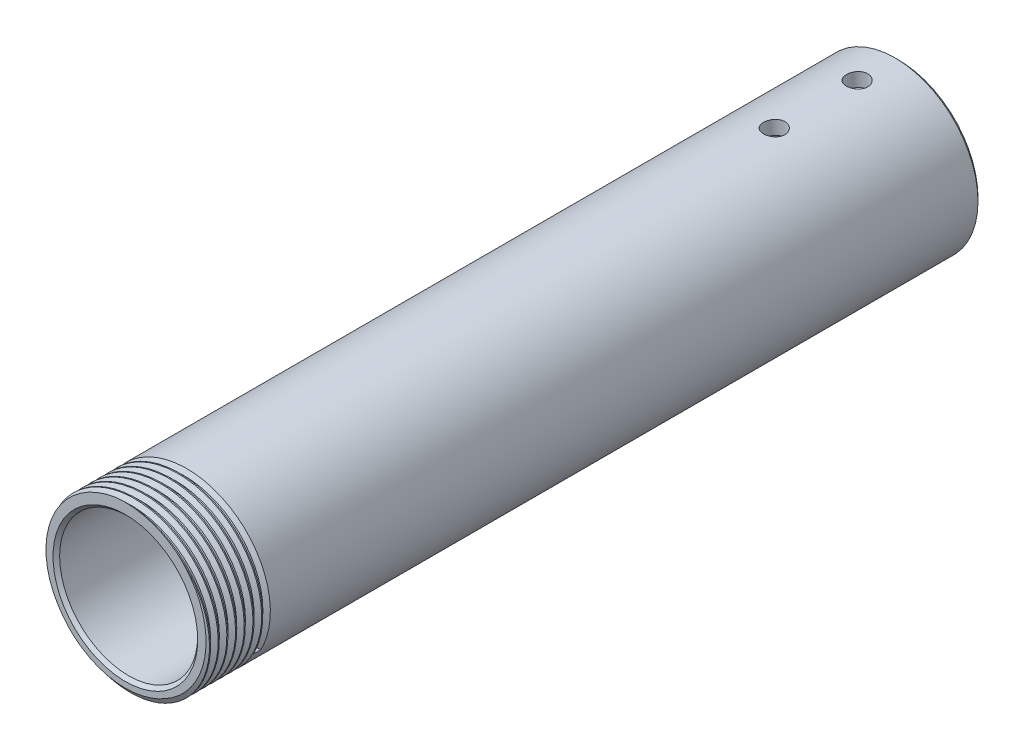
SolidWorks part; units mm, degrees
material "6061-T6 (SS)"
ref_plane "Front Plane" through (0, 0, 0) normal (0, 0, 1) x (1, 0, 0)
ref_plane "Top Plane" through (0, 0, 0) normal (0, 1, 0) x (1, 0, 0)
ref_plane "Right Plane" through (0, 0, 0) normal (1, 0, 0) x (0, 0, -1)
sketch "Sketch1" plane through (0, 0, 0) normal (0, 0, 1) x (1, 0, 0)
  circle A0 centre (0, 0) radius 15.875
  circle A1 centre (0, 0) radius 19.05
  dimension "D1" = 31.75
  dimension "D2" = 3.175
extrude "Boss-Extrude1" add sketch "Sketch1" along normal blind 177.8
ref_plane "Rear Tangent Plane" through (0, 19.05, 0) normal (0, 1, 0) x (1, 0, 0)
hole_wizard "#8 Clearance Hole1" positions "Sketch2" profile "Sketch3" hole size "#8" standard "ANSI Inch" end condition through all
sketch "Sketch2" plane through (0, 19.05, 0) normal (0, 1, 0) x (1, 0, 0)
  point P0 (0, -9.525)
  point P3 (0, -28.575)
sketch "Sketch3" plane through (0, 19.05, 9.525) normal (1, 0, 0) x (0, 0, 1)
  line L0 (0, 0) -> (0, 38.1)
  line L1 (0, 38.1) -> (2.4574, 38.1)
  line L2 (2.4574, 38.1) -> (2.4574, 0)
  line L5 (2.4574, 0) -> (0, 0)
  line L11 (0, -6.35) -> (0, 107.95) construction
  dimension "Thru Hole Dia." = 4.9149
  dimension "Thru Hole Depth" = 38.1
ref_plane "FWD Tangent Plane" through (0, -19.05, 0) normal (0, -1, 0) x (-1, 0, 0)
hole_wizard "#8 Clearance Hole2" positions "Sketch4" profile "Sketch5" hole size "#8" standard "ANSI Inch"
sketch "Sketch4" plane through (0, -19.05, 0) normal (0, -1, 0) x (-1, 0, 0)
  circle A0 centre (0, -107.1562) radius 2.4574 construction
  circle A1 centre (0, -69.0562) radius 2.4575 construction
  point P0 (0, -107.1562)
  point P2 (0, -69.0562)
sketch "Sketch5" plane through (0, -19.05, 107.1562) normal (1, 0, 0) x (0, 0, -1)
  line L0 (0, 0) -> (0, 3.175)
  line L1 (0, 3.175) -> (2.4574, 3.175)
  line L2 (2.4574, 3.175) -> (2.4574, 0)
  line L5 (2.4574, 0) -> (0, 0)
  line L11 (0, -6.35) -> (0, 107.95) construction
  dimension "Thru Hole Dia." = 4.9149
  dimension "Thru Hole Depth" = 3.175
hole_wizard "1/2 (0.5) Diameter Hole1" positions "Sketch6" profile "Sketch7" hole size "1/2" standard "ANSI Inch"
sketch "Sketch6" plane through (0, -19.05, 0) normal (0, -1, 0) x (-1, 0, 0)
  circle A0 centre (0, -88.1062) radius 12.7 construction
  point P0 (0, -88.1062)
sketch "Sketch7" plane through (0, -19.05, 88.1062) normal (1, 0, 0) x (0, 0, -1)
  line L0 (0, 0) -> (0, 3.175)
  line L1 (0, 3.175) -> (6.35, 3.175)
  line L2 (6.35, 3.175) -> (6.35, 0)
  line L5 (6.35, 0) -> (0, 0)
  line L11 (0, -6.35) -> (0, 107.95) construction
  dimension "Thru Hole Dia." = 12.7
  dimension "Thru Hole Depth" = 3.175
thread "M36-2.0 X 12.7 Thread" pitch 2 start angle 0, offset 2.46, length 12.7, pitch 2, diameter 38.1
ref_plane "Plane2" through (-19.05, 0, 180.26) normal (0, -1, 0) x (-1, 0, 0)
sketch "Thread Profile1" plane through (-19.05, 0, 180.26) normal (0, -1, 0) x (-1, 0, 0)
  line L0 (0, 0) -> (0, 2) construction
  line L11 (0, 0) -> (0, 1.75)
  line L12 (0, 1.75) -> (-1.0825, 1.125)
  line L13 (-1.0825, 1.125) -> (-1.0825, 0.625)
  line L15 (-1.0825, 0.625) -> (0, 0)
  line L17 (-1.0825, 0.875) -> (0, 0.875) construction
  point P2 (0, 0)
  dimension "Pitch" = 2
  dimension "Profile_Angle" = 60
  dimension "Profile_Land" = 0.5
  dimension "Profile_Height" = 1.0825
chamfer "Chamfer1" distance 0.762 angle 45 3 edges at (15.875, 0, 177.8) (19.05, 0, 0) (15.875, 0, 0)
